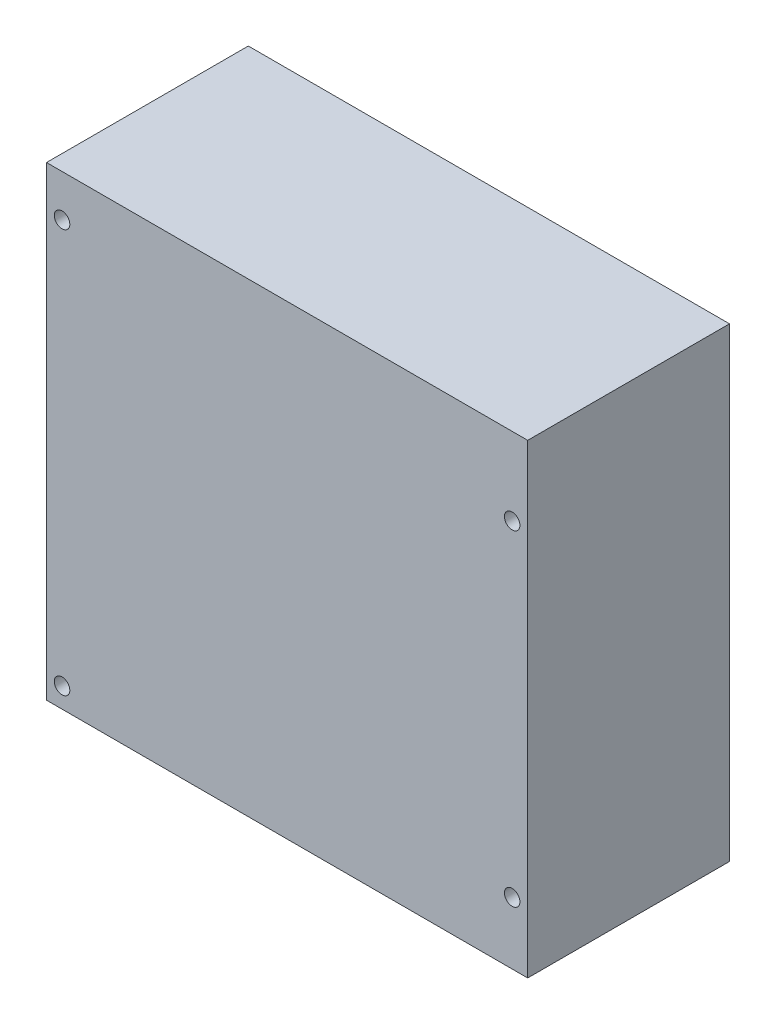
SolidWorks part; units mm, degrees
ref_plane "Front Plane" through (0, 0, 0) normal (0, 0, 1) x (1, 0, 0)
ref_plane "Top Plane" through (0, 0, 0) normal (0, 1, 0) x (1, 0, 0)
ref_plane "Right Plane" through (0, 0, 0) normal (1, 0, 0) x (0, 0, -1)
sketch "Sketch1" plane through (0, 0, 0) normal (0, 0, 1) x (1, 0, 0)
  line L2 (-39.37, -38.1) -> (39.37, -38.1)
  line L3 (-39.37, -38.1) -> (-39.37, 38.1)
  line L4 (-39.37, 38.1) -> (39.37, 38.1)
  line L5 (39.37, -38.1) -> (39.37, 38.1)
  line L6 (-39.37, -38.1) -> (39.37, 38.1) construction
  line L7 (-39.37, 38.1) -> (39.37, -38.1) construction
  circle A0 centre (36.83, 25.4) radius 1.27
  circle A1 centre (36.83, -27.94) radius 1.27
  circle A2 centre (-36.83, 31.242) radius 1.27
  circle A3 centre (-36.83, -34.798) radius 1.27
  point P2 (0, 0)
  dimension "D5" = 2.54
  dimension "D6" = 2.54
  dimension "D7" = 2.54
  dimension "D11" = 2.54
  dimension "D12" = 2.54
  dimension "D13" = 53.34
  dimension "D1" = 78.74
  dimension "D2" = 76.2
  dimension "D3" = 10.16
  dimension "D4" = 2.54
  dimension "D8" = 2.54
  dimension "D9" = 66.04
  dimension "D10" = 3.302
extrude "Boss-Extrude1" add sketch "Sketch1" along normal blind 33.02
sketch "Sketch2" plane through (0, 0, 0) normal (0, 0, -1) x (-1, 0, 0)
  circle A0 centre (-36.83, 25.4) radius 1.27
  circle A1 centre (36.83, 31.242) radius 1.27
  circle A2 centre (36.83, -34.798) radius 1.27
  circle A3 centre (36.83, -34.798) radius 1.27
  circle A4 centre (-36.83, -27.94) radius 1.27
extrude "Boss-Extrude2" add sketch "Sketch2" against normal blind 2.54 contours A0
sketch "Sketch3" plane through (0, 0, 0) normal (0, 0, -1) x (-1, 0, 0)
  circle A0 centre (36.83, 31.242) radius 1.27
  circle A1 centre (36.83, -34.798) radius 1.27
  circle A2 centre (-36.83, -27.94) radius 1.27
extrude "Boss-Extrude3" add sketch "Sketch3" against normal blind 2.54
ref_axis "Axis1" through (-36.83, -34.798, 33.02) along (0, 0, -1)
ref_axis "Axis2" through (-36.83, 31.242, 33.02) along (0, 0, -1)
ref_axis "Axis3" through (36.83, -27.94, 33.02) along (0, 0, -1)
ref_axis "Axis4" through (36.83, 25.4, 33.02) along (0, 0, -1)
equation "\"Uno32\"= 1.3"
equation "\"D1@Boss-Extrude1\"=\"Uno32\""
